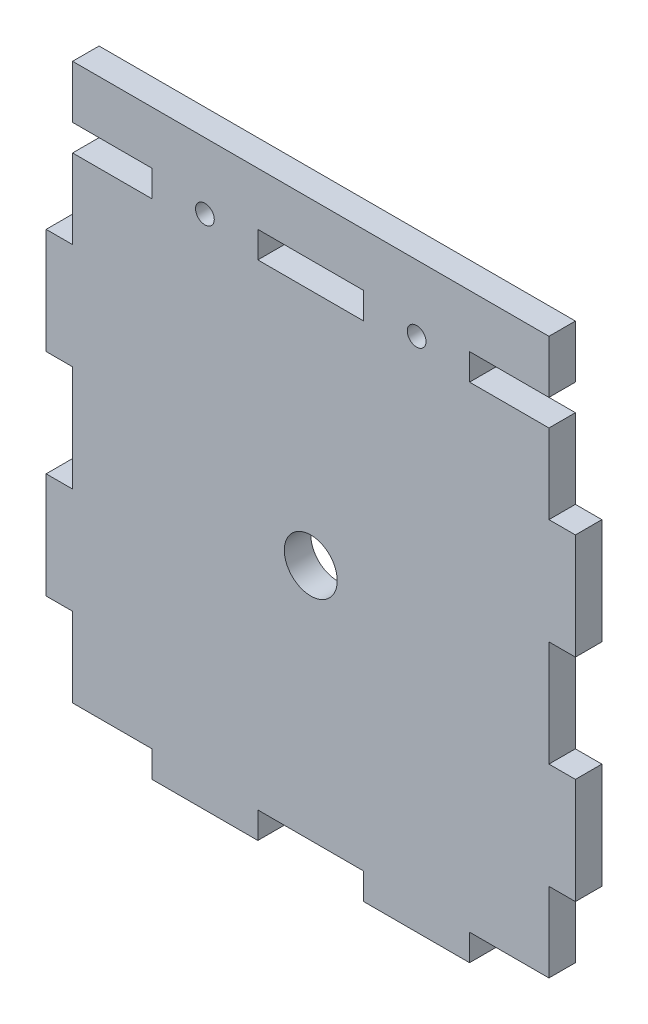
SolidWorks part; units mm, degrees
ref_plane "Front Plane" through (0, 0, 0) normal (0, 0, 1) x (1, 0, 0)
ref_plane "Top Plane" through (0, 0, 0) normal (0, 1, 0) x (1, 0, 0)
ref_plane "Right Plane" through (0, 0, 0) normal (1, 0, 0) x (0, 0, -1)
sketch "Sketch1" plane through (0, 0, 0) normal (0, 0, 1) x (1, 0, 0)
  line L1 (0, 0) -> (127, 0)
  line L2 (0, 0) -> (0, 139.7)
  line L3 (0, 139.7) -> (127, 139.7)
  line L4 (127, 0) -> (127, 139.7)
  dimension "D1" = 127
  dimension "D2" = 139.7
extrude "Boss-Extrude1" add sketch "Sketch1" along normal blind 6.35
sketch "Sketch5" plane through (0, 0, 6.35) normal (0, 0, 1) x (1, 0, 0)
  line L1 (0, 0) -> (6.35, 0)
  line L2 (0, 0) -> (0, 25.4)
  line L3 (0, 25.4) -> (6.35, 25.4)
  line L4 (6.35, 0) -> (6.35, 25.4)
  dimension "D1" = 25.4
  dimension "D2" = 6.35
extrude "Cut-Extrude4" cut sketch "Sketch5" against normal blind 6.35
sketch "Sketch6" plane through (0, 0, 6.35) normal (0, 0, 1) x (1, 0, 0)
  line L1 (0, 0) -> (25.4, 0)
  line L2 (0, 0) -> (0, 6.35)
  line L3 (0, 6.35) -> (25.4, 6.35)
  line L4 (25.4, 0) -> (25.4, 6.35)
  dimension "D1" = 6.35
  dimension "D2" = 25.4
extrude "Cut-Extrude5" cut sketch "Sketch6" against normal blind 6.35
pattern_linear "LPattern5" count 3 spacing 50.8 along (0, 1, 0) count 2 spacing 120.65 along (1, 0, 0) of "Cut-Extrude4"
pattern_linear "LPattern6" count 3 spacing 50.8 along (1, 0, 0) count 2 spacing 120.65 along (0, 1, 0) of "Cut-Extrude5"
sketch "Sketch7" plane through (0, 0, 6.35) normal (0, 0, 1) x (1, 0, 0)
  line L0 (127, 127) -> (101.6, 127) construction
  line L1 (6.35, 120.65) -> (0, 120.65)
  line L2 (6.35, 120.65) -> (6.35, 139.7)
  line L3 (6.35, 139.7) -> (0, 139.7)
  line L4 (0, 120.65) -> (0, 139.7)
  line L5 (127, 139.7) -> (120.65, 139.7)
  line L6 (127, 139.7) -> (127, 127)
  line L7 (127, 127) -> (120.65, 127)
  line L8 (120.65, 139.7) -> (120.65, 127)
  dimension "D1" = 6.35
  dimension "D2" = 19.05
  dimension "D3" = 6.35
extrude "Cut-Extrude6" cut sketch "Sketch7" against normal blind 6.35
hole_wizard "#8 Clearance Hole1" positions "Sketch10" profile "Sketch9" hole size "#8" standard "ANSI Inch"
sketch "Sketch10" plane through (0, 0, 6.35) normal (0, 0, 1) x (1, 0, 0)
  line L2 (25.4, 120.65) -> (25.4, 127) construction
  line L3 (76.2, 127) -> (50.8, 127) construction
  line L4 (76.2, 120.65) -> (76.2, 127) construction
  point P0 (38.1, 123.825)
  point P2 (88.9, 123.825)
  point P10 (25.4, 123.825)
  dimension "D1" = 12.7
  dimension "D3" = 12.7
  dimension "D4" = 3.175
sketch "Sketch9" plane through (38.1, 123.825, 6.35) normal (1, 0, 0) x (0, -1, 0)
  line L0 (0, 0) -> (0, 11.5107)
  line L1 (0, 11.5107) -> (2.2479, 10.16)
  line L2 (2.2479, 10.16) -> (2.2479, 0)
  line L5 (2.2479, 0) -> (0, 0)
  line L10 (0, 11.5107) -> (-2.2479, 10.16) construction
  line L11 (0, -6.35) -> (0, 107.95) construction
  dimension "Hole Dia." = 4.4958
  dimension "Hole Depth" = 10.16
  dimension "Drill Angle" = 118
sketch "Sketch11" plane through (0, 0, 6.35) normal (0, 0, 1) x (1, 0, 0)
  circle A0 centre (63.5, 63.5) radius 6.35
  dimension "D1" = 12.7
extrude "Cut-Extrude7" cut sketch "Sketch11" against normal blind 7.62
